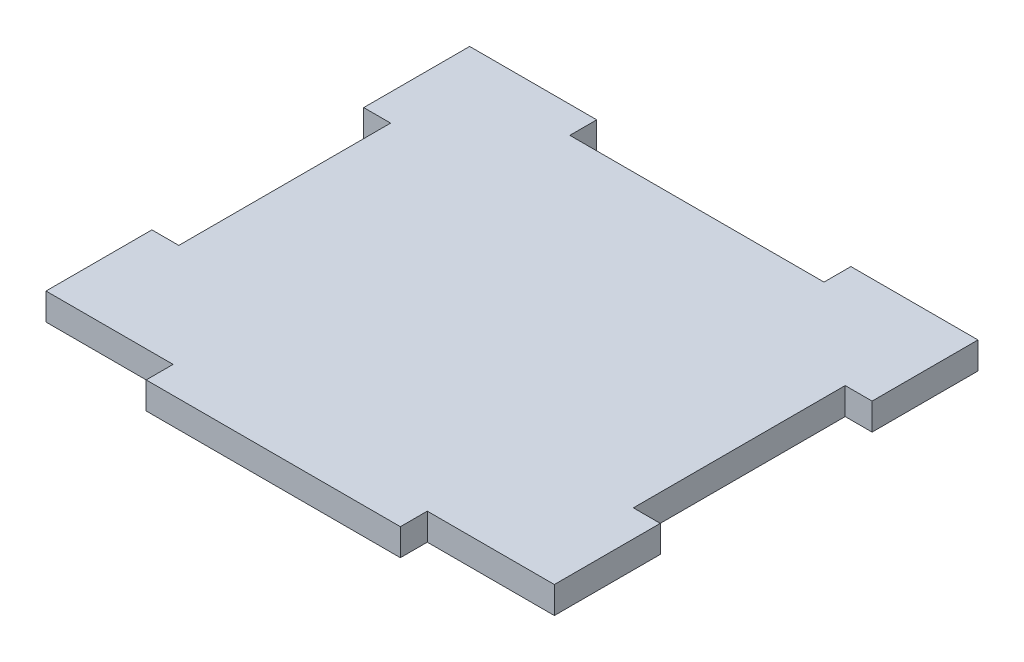
SolidWorks part; units mm, degrees
ref_plane "Front Plane" through (0, 0, 0) normal (0, 0, 1) x (1, 0, 0)
ref_plane "Top Plane" through (0, 0, 0) normal (0, 1, 0) x (1, 0, 0)
ref_plane "Right Plane" through (0, 0, 0) normal (1, 0, 0) x (0, 0, -1)
sketch "Sketch1" plane through (0, 0, 0) normal (0, 1, 0) x (1, 0, 0)
  line L1 (-30, -25) -> (30, -25)
  line L2 (-30, -25) -> (-30, 25)
  line L3 (-30, 25) -> (30, 25)
  line L4 (30, -25) -> (30, 25)
  line L5 (-30, -25) -> (30, 25) construction
  line L6 (-30, 25) -> (30, -25) construction
  point P0 (0, 0)
  dimension "D1" = 60
  dimension "D2" = 50
extrude "Boss-Extrude1" add sketch "Sketch1" along normal blind 3.175
sketch "Sketch2" plane through (0, 3.175, 0) normal (0, 1, 0) x (1, 0, 0)
  line L0 (30, 25) -> (-30, 25) construction
  line L1 (-15, 25) -> (15, 25)
  line L2 (-15, 25) -> (-15, 21.825)
  line L3 (-15, 21.825) -> (15, 21.825)
  line L4 (15, 25) -> (15, 21.825)
  line L5 (-15, 21.825) -> (-30, 21.825) construction
  line L6 (-30, 25) -> (-30, -25) construction
  line L7 (15, 21.825) -> (30, 21.825) construction
  line L8 (30, -25) -> (30, 25) construction
  dimension "D1" = 30
  dimension "D2" = 3.175
extrude "Cut-Extrude1" cut sketch "Sketch2" against normal through all
sketch "Sketch3" plane through (0, 3.175, 0) normal (0, 1, 0) x (1, 0, 0)
  line L0 (-15, 21.825) -> (15, 21.825) construction
  line L1 (15, 21.825) -> (15, 25) construction
  line L2 (-15, 25) -> (-15, 21.825) construction
  line L3 (-30, -25) -> (30, -25) construction
  line L4 (-15, 21.825) -> (15, 21.825)
  line L5 (15, 21.825) -> (15, 25)
  line L6 (-15, 25) -> (-15, 21.825)
  line L7 (-30, -25) -> (30, -25)
  line L8 (-15, 21.825) -> (-15, -25) construction
  line L9 (15, 21.825) -> (15, -25) construction
  line L10 (-15, -25) -> (-15, -28.175)
  line L11 (-15, -28.175) -> (15, -28.175)
  line L12 (15, -28.175) -> (15, -25)
  line L13 (-15, -25) -> (15, -25)
  dimension "D1" = 3.175
extrude "Boss-Extrude2" add sketch "Sketch3" against normal up to surface (3.175 mm away) contours L11 L12 L7 L10 region at (0, 3.175, 26.5875) up to face at (0, 0, -11.7063)
sketch "Sketch5" plane through (0, 3.175, 0) normal (0, 1, 0) x (1, 0, 0)
  line L0 (-30, 25) -> (-30, -25) construction
  line L1 (-30, 12.5) -> (-26.825, 12.5)
  line L2 (-30, 12.5) -> (-30, -12.5)
  line L3 (-30, -12.5) -> (-26.825, -12.5)
  line L4 (-26.825, 12.5) -> (-26.825, -12.5)
  line L5 (0, -28.175) -> (0, 21.825) construction
  line L6 (-15, -28.175) -> (15, -28.175) construction
  line L7 (-15, 21.825) -> (15, 21.825) construction
  line L8 (-26.825, 25) -> (-26.825, 12.5) construction
  line L9 (-15, 25) -> (-30, 25) construction
  line L10 (-26.825, -12.5) -> (-26.825, -25) construction
  line L11 (-30, -25) -> (-15, -25) construction
  line L12 (26.825, -12.5) -> (26.825, -25) construction
  line L13 (26.825, 25) -> (26.825, 12.5) construction
  line L14 (26.825, 12.5) -> (26.825, -12.5)
  line L15 (30, -12.5) -> (26.825, -12.5)
  line L16 (30, 12.5) -> (30, -12.5)
  line L17 (30, 12.5) -> (26.825, 12.5)
  dimension "D1" = 3.175
  dimension "D2" = 25
extrude "Cut-Extrude2" cut sketch "Sketch5" against normal blind 3.175
